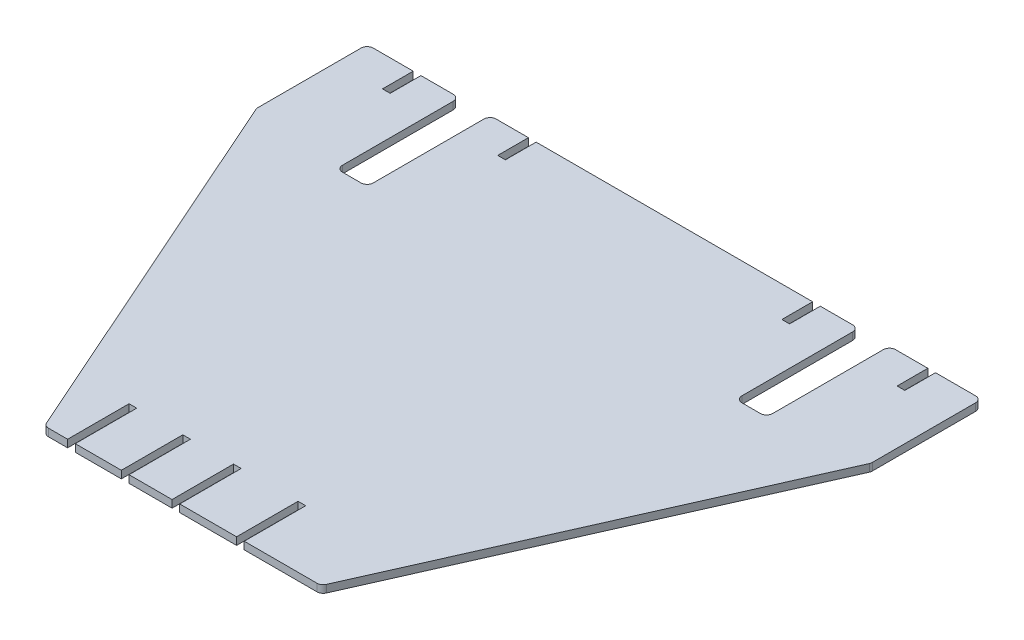
SolidWorks part; units mm, degrees
material "Corrugated Paper"
ref_plane "Front Plane" through (0, 0, 0) normal (0, 0, 1) x (1, 0, 0)
ref_plane "Top Plane" through (0, 0, 0) normal (0, 1, 0) x (1, 0, 0)
ref_plane "Right Plane" through (0, 0, 0) normal (1, 0, 0) x (0, 0, -1)
sketch "Sketch1" plane through (0, 0, 0) normal (0, 1, 0) x (1, 0, 0)
  line L0 (0, 0) -> (0, -142.875) construction
  line L3 (3.3512, -101.6) -> (-1.27, -101.6)
  line L4 (-57.15, -101.6) -> (-127, 55.88)
  line L5 (-127, 55.88) -> (-127, 101.6)
  line L6 (-127, 101.6) -> (-107.95, 101.6)
  line L7 (-88.9, 101.6) -> (-88.9, 50.8)
  line L9 (-88.9, 50.8) -> (-76.2, 50.8)
  line L10 (-76.2, 50.8) -> (-76.2, 101.6)
  line L11 (-76.2, 101.6) -> (-60.325, 101.6)
  line L13 (76.2, 50.8) -> (76.2, 101.6)
  line L14 (88.9, 50.8) -> (76.2, 50.8)
  line L15 (88.9, 101.6) -> (88.9, 50.8)
  line L16 (127, 101.6) -> (107.95, 101.6)
  line L17 (127, 55.88) -> (127, 101.6)
  line L18 (57.15, -101.6) -> (127, 55.88)
  line L19 (3.3512, -101.6) -> (22.225, -101.6)
  line L21 (-127, 101.6) -> (127, -101.6) construction
  line L22 (-25.4, -101.6) -> (-44.45, -101.6)
  line L24 (-25.4, -101.6) -> (-25.4, -76.2)
  line L25 (-25.4, -76.2) -> (-22.225, -76.2)
  line L26 (-22.225, -101.6) -> (-22.225, -76.2)
  line L27 (25.4, -101.6) -> (25.4, -76.2)
  line L28 (25.4, -76.2) -> (22.225, -76.2)
  line L29 (22.225, -101.6) -> (22.225, -76.2)
  line L30 (25.4, -101.6) -> (57.15, -101.6)
  line L31 (-82.55, 50.8) -> (-82.55, 101.6) construction
  line L32 (-104.775, 101.6) -> (-88.9, 101.6)
  line L34 (-107.95, 101.6) -> (-107.95, 88.9)
  line L35 (-107.95, 88.9) -> (-104.775, 88.9)
  line L36 (-104.775, 101.6) -> (-104.775, 88.9)
  line L37 (-57.15, 101.6) -> (-57.15, 88.9)
  line L38 (-57.15, 88.9) -> (-60.325, 88.9)
  line L39 (-60.325, 101.6) -> (-60.325, 88.9)
  line L40 (-57.15, 101.6) -> (57.15, 101.6)
  line L41 (107.95, 101.6) -> (107.95, 88.9)
  line L42 (107.95, 88.9) -> (104.775, 88.9)
  line L43 (104.775, 101.6) -> (104.775, 88.9)
  line L44 (57.15, 101.6) -> (57.15, 88.9)
  line L45 (60.325, 101.6) -> (60.325, 88.9)
  line L46 (57.15, 88.9) -> (60.325, 88.9)
  line L47 (60.325, 101.6) -> (76.2, 101.6)
  line L48 (104.775, 101.6) -> (88.9, 101.6)
  line L49 (-47.625, -101.6) -> (-47.625, -76.2)
  line L50 (-47.625, -76.2) -> (-44.45, -76.2)
  line L51 (-44.45, -76.2) -> (-44.45, -101.6)
  line L52 (-47.625, -101.6) -> (-57.15, -101.6)
  line L53 (-4.445, -101.6) -> (-4.445, -76.2)
  line L54 (-4.445, -76.2) -> (-1.27, -76.2)
  line L55 (-1.27, -76.2) -> (-1.27, -101.6)
  line L56 (-4.445, -101.6) -> (-22.225, -101.6)
  point P51 (3.3512, -101.6)
  dimension "D3" = 254
  dimension "D6" = 50.8
  dimension "D7" = 203.2
  dimension "D8" = 45.72
  dimension "D10" = 3.175
  dimension "D11" = 25.4
  dimension "D12" = 3.175
  dimension "D4" = 114.3
  dimension "D13" = 50.8
  dimension "D9" = 50.8
  dimension "D14" = 38.1
  dimension "D15" = 12.7
  dimension "D16" = 19.05
  dimension "D2" = 24.13
  dimension "D5" = 12.7
extrude "Boss-Extrude1" add sketch "Sketch1" along normal blind 3.0988 contours L13 L47 L45 L46 L44 L40 L37 L38 L39 L11 L10 L9 L7 L32 L36 L35 L34 L6 L5 L4 L52 L49 L50 L51 L22 L24 L25 L26 L56 L53 L54 L55 L3 L19 L29 L28 L27 L30 L18 L17 L16 L41 L42 L43 L48 L15 L14
fillet "Fillet1" radius 2.54 14 edges at (88.9, 1.5494, -50.8) (88.9, 1.5494, -101.6) (-127, 1.5494, -55.88) (-127, 1.5494, -101.6) (-88.9, 1.5494, -101.6) (-88.9, 1.5494, -50.8) (-76.2, 1.5494, -50.8) (-76.2, 1.5494, -101.6) (76.2, 1.5494, -101.6) (76.2, 1.5494, -50.8) (127, 1.5494, -101.6) (127, 1.5494, -55.88) (57.15, 1.5494, 101.6) (-57.15, 1.5494, 101.6)
sketch "Sketch4" plane through (0, 3.0988, 0) normal (0, 1, 0) x (1, 0, 0)
  line L0 (0, -164.31) -> (0, 101.6) construction
  line L1 (-63.105, 101.6) -> (63.105, 101.6) construction
  line L2 (-63.105, 101.6) -> (-63.105, -164.31) construction
  line L3 (-63.105, -164.31) -> (63.105, -164.31) construction
  line L4 (63.105, 101.6) -> (63.105, -164.31) construction
  line L5 (57.8198, -100.0899) -> (126.7819, 55.3882) construction
  line L6 (65.3301, -83.1577) -> (50.405, -83.1577)
  line L7 (65.3301, -83.1577) -> (65.3301, -88.1742)
  line L8 (65.3301, -88.1742) -> (50.405, -88.1742)
  line L9 (50.405, -83.1577) -> (50.405, -88.1742)
  line L10 (-50.405, -83.1577) -> (-50.405, -88.1742)
  line L11 (-65.3301, -88.1742) -> (-50.405, -88.1742)
  line L12 (-65.3301, -83.1577) -> (-65.3301, -88.1742)
  line L13 (-65.3301, -83.1577) -> (-50.405, -83.1577)
  line L14 (-57.15, 101.6) -> (57.15, 101.6) construction
  line L15 (-1.5875, 101.6) -> (1.5875, 101.6)
  line L16 (-1.5875, 101.6) -> (-1.5875, 88.9)
  line L17 (-1.5875, 88.9) -> (1.5875, 88.9)
  line L18 (1.5875, 101.6) -> (1.5875, 88.9)
  point P8 (63.105, -88.1742)
  point P11 (0, 101.6)
  dimension "D1" = 265.91
  dimension "D2" = 126.21
  dimension "D5" = 3.175
  dimension "D6" = 12.7
  dimension "D4" = 12.7
  dimension "D3" = 5.0165
extrude "Cut-Extrude3" [suppressed] cut sketch "Sketch4" against normal through all
equation "\"D1@Boss-Extrude1\" = \"thick\""
equation "\"D10@Sketch1\"=\"thick\"+\"clear\""
equation "\"D12@Sketch1\"=\"thick\"+\"clear\""
equation "\"rodThick\"= 0.085in"
equation "\"thick\"= 0.122in"
equation "\"clear\"= 0.003in"
equation "\"D5@Sketch4\"=\"thick\"+\"clear\""
